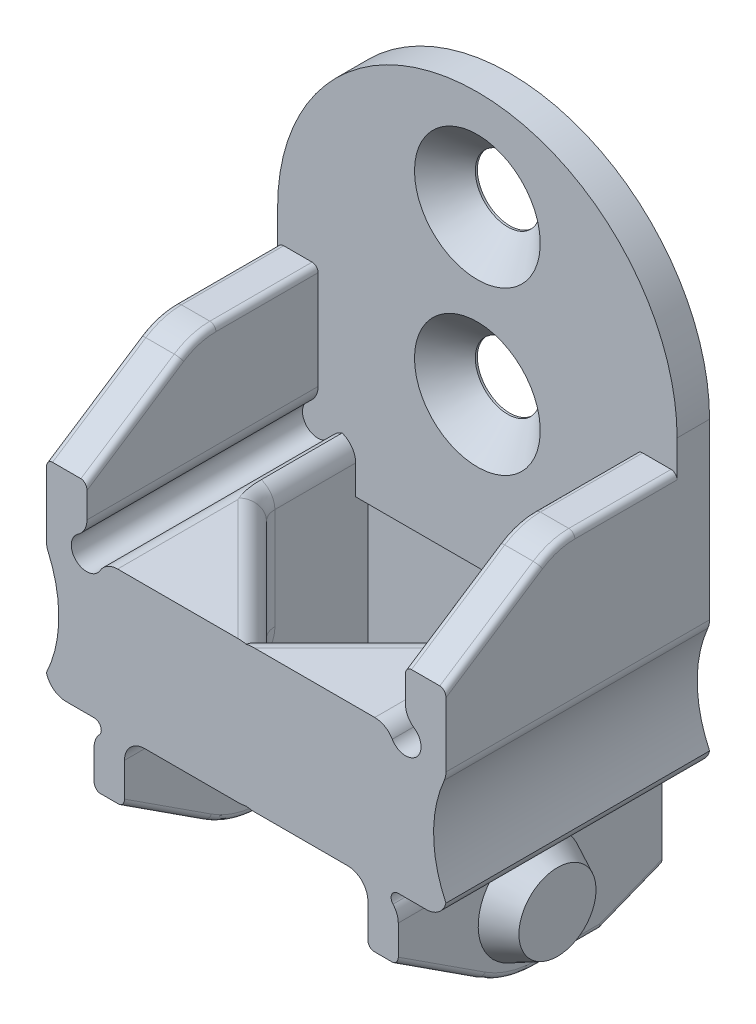
SolidWorks part; units mm, degrees
material "PS HI"
ref_plane "Спереди" through (0, 0, 0) normal (0, 0, 1) x (1, 0, 0)
ref_plane "Сверху" through (0, 0, 0) normal (0, 1, 0) x (1, 0, 0)
ref_plane "Справа" through (0, 0, 0) normal (1, 0, 0) x (0, 0, -1)
sketch "Эскиз1" plane through (0, 0, 0) normal (0, 0, 1) x (1, 0, 0)
  line L0 (0, 5.8222) -> (0, -7.793) construction
  line L1 (-6, -3.5) -> (0, -3.5)
  line L3 (-7.1103, 3.5) -> (0, 3.5)
  line L7 (-7.85, -3.4318) -> (-9.85, -3.4318)
  line L8 (-7.85, 4.1458) -> (-7.85, 10)
  line L9 (-7.85, 10) -> (-9.85, 10)
  line L10 (-9.85, -3.4318) -> (-9.85, 10)
  line L11 (-7.85, -3.4318) -> (-7.5, -3.4318)
  line L14 (-7.5, -4.1389) -> (-7.5, -10)
  line L17 (-7.5, -4.1389) -> (-7.5, -10)
  line L18 (-7.5, -10) -> (-6, -10)
  line L19 (-6, -3.5) -> (-6, -10)
  arc A0 (-7.5, -3.4318) -> (-7.5, -4.1389) centre (-7.5, -3.7853) cw
  arc A1 (-7.85, 4.1458) -> (-7.1103, 3.5) centre (-7.8627, 3.3848) ccw
  point P0 (0, 0)
  dimension "D1" = 2
  dimension "D2" = 7
  dimension "D3" = 0.35
  dimension "D4" = 6.5
  dimension "D5" = 6.5
  dimension "D6" = 1.5
  dimension "D7" = 6
  dimension "D8" = 3.5
  dimension "D9" = 9.85
extrude "Бобышка-Вытянуть1" add sketch "Эскиз1" along normal blind 13
chamfer "Фаска1" distance 5.4 angle 33.3 1 edges at (-8.85, 10, 13)
sketch "Эскиз2" plane through (0, 3.5, 0) normal (0, 1, 0) x (1, 0, 0)
  line L0 (0, -13) -> (0, 0) construction
  line L1 (0, -1) -> (-6, -1)
  line L2 (0, -1) -> (0, -12)
  line L3 (0, -12) -> (-6, -12)
  line L4 (-6, -1) -> (-6, -12)
  line L5 (-7.1103, 0) -> (0, 0) construction
  line L6 (-7.1103, -13) -> (0, -13) construction
  line L7 (-6, -13) -> (-6, 0) construction
  dimension "D1" = 1
  dimension "D2" = 1
extrude "Вырез-Вытянуть1" cut sketch "Эскиз2" against normal through all
ref_plane "Плоскость1" through (0, 0, 6.5) normal (0, 0, -1) x (-1, 0, 0)
fillet "Скругление3" radius 3.2 1 edges at (-8.85, 10, 7.6)
sketch "Эскиз5" plane through (-7.5, 0, 0) normal (-1, 0, 0) x (0, 0, 1)
  line L0 (0, -10) -> (0, -8.8044)
  line L1 (0, -4.1389) -> (0, -10) construction
  line L3 (0, -8.8044) -> (3.0199, -10)
  line L4 (13, -10) -> (0, -10) construction
  line L5 (3.0199, -10) -> (0, -10)
extrude "Вырез-Вытянуть2" cut sketch "Эскиз5" against normal up to next
sketch "Эскиз7" plane through (0, 0, 13) normal (0, 0, 1) x (1, 0, 0)
  line L0 (-9.85, -3.4318) -> (-9.85, 6.4529) construction
  line L1 (-9.85, 2.7085) -> (-9.85, -2.673)
  line L2 (-9.85, -3.4318) -> (-9.85, 6.4529) construction
  arc A0 (-9.85, -2.673) -> (-9.85, 2.7085) centre (-15.4901, 0.0178) ccw
extrude "Вырез-Вытянуть4" cut sketch "Эскиз7" against normal up to next
sketch "Эскиз10" plane through (0, 0, 6.5) normal (0, 0, -1) x (-1, 0, 0)
  line L0 (9.6131, -6.8) -> (2.6205, -6.8) construction
  line L1 (6, -3.5) -> (0, -3.5) construction
  line L2 (13.5674, 6.8) -> (4.1326, 6.8) construction
  line L3 (7.1103, 3.5) -> (0, 3.5) construction
  line L4 (7.85, 6.8) -> (8.85, 6.8)
  line L5 (8.85, 6.8) -> (8.85, 8.8)
  line L6 (8.85, 8.8) -> (7.85, 9.2877)
  line L8 (7.85, 9.2877) -> (7.85, 6.8)
  line L10 (7.5, -6.8) -> (7.5, -4.2416)
  line L11 (7.5, -4.1389) -> (7.5, -10) construction
  line L12 (7.5, -4.2416) -> (8.85, -4.9)
  line L13 (8.85, -4.9) -> (8.85, -6.8)
  line L14 (8.85, -6.8) -> (7.5, -6.8)
  line L17 (7.85, 9.4746) -> (7.85, 6.4529) construction
  dimension "D1" = 3.3
  dimension "D2" = 3.3
  dimension "D3" = 2
  dimension "D4" = 1
  dimension "D5" = 64
  dimension "D6" = 64
  dimension "D7" = 1.9
revolve "Повернуть2" add sketch "Эскиз10" angle 360 about L0
sketch "Эскиз11" plane through (-6, 0, 0) normal (1, 0, 0) x (0, 0, -1)
  line L0 (-7.6293, -10) -> (-13, -6.5141)
  line L1 (-13, -10) -> (-3.0199, -10) construction
  line L2 (-13, -3.5) -> (-13, -10) construction
  line L4 (-13, -6.5141) -> (-13, -10)
  line L5 (-13, -10) -> (-7.6293, -10)
extrude "Вырез-Вытянуть7" cut sketch "Эскиз11" against normal blind 10
fillet "Скругление7" radius 5 1 edges at (-6.75, -10, 7.6293)
chamfer "Фаска2" distance 6 angle 45 1 edges at (-6, 0, 12)
sketch "Эскиз12" plane through (0, 0, 1) normal (0, 0, 1) x (1, 0, 0)
  line L0 (-6, -3.5) -> (-6, -8.8044)
  line L1 (-6, -8.8044) -> (0, -8.8044)
  line L2 (0, -8.8044) -> (0, -3.5)
  line L4 (0, -3.5) -> (-6, -3.5)
extrude "Бобышка-Вытянуть2" add sketch "Эскиз12" against normal up to surface (1 mm away) up to face at (-6.9022, -0.3887, 0)
fillet "Скругление11" radius 1 5 edges at (-6, 3.5, 3.5) (-3, 3.5, 9) (-3, -3.5, 9) (-6, 0, 6) (-6, -3.5, 9.5)
fillet "Скругление13" radius 1 2 edges at (-9.85, 2.7085, 6.5) (-9.85, -3.4318, 6.5)
fillet "Скругление12" radius 1 3 edges at (-7.5, -4.1389, 6.5) (-7.1103, 3.5, 6.5) (-7.85, 4.1458, 6.5)
fillet "Скругление14" radius 0.3 14 edges at (-7.5, -10, 4.5844) (-7.5, -7.8541, 10.9355) (-6, -7.8541, 10.9355) (-6, -9.7943, 7.5683) (-9.85, 7.9637, 10.6999) (-9.85, 9.8658, 7.5599) (-7.85, 7.9637, 10.6999) (-7.85, 9.8658, 7.5599) (-7.5, -9.7943, 7.5683) (-7.5, -9.4022, 1.51) (-6, -9.4022, 1.51) (-6, -10, 4.5844) (-9.85, 10, 3.3215) (-7.85, 10, 3.3215)
sketch "Эскиз13" plane through (0, 0, 0) normal (0, 0, -1) x (-1, 0, 0)
  line L0 (7.85, 4.8432) -> (7.85, 9.7) construction
  line L1 (9.85, 2.9261) -> (9.85, 9.7) construction
  line L2 (7.85, 7.4921) -> (9.85, 7.4921)
  arc A0 (7.85, 7.4921) -> (9.85, 7.4921) centre (8.85, 9.9699) cw
extrude "Бобышка-Вытянуть3" [suppressed] add sketch "Эскиз13" against normal blind 0.2
sketch "Эскиз15" plane through (0, 0, 0) normal (0, 0, -1) x (-1, 0, 0)
  line L3 (0, 3.5) -> (0, -8.8044) construction
  line L4 (0, 1.9519) -> (9.0645, 1.9519)
  line L5 (9.85, 2.9261) -> (9.85, 11.4926)
  line L6 (0, 21.3426) -> (0, 18.0257)
  line L7 (9.0645, 1.9519) -> (9.85, 2.9261)
  line L8 (0, 14.8257) -> (0, 10.0257)
  line L9 (0, 6.8257) -> (0, 1.9519)
  arc A1 (9.85, 11.4926) -> (0, 21.3426) centre (0, 11.4926) ccw
  arc A2 (0, 14.8257) -> (0, 18.0257) centre (0, 16.4257) ccw
  arc A3 (0, 6.8257) -> (0, 10.0257) centre (0, 8.4257) ccw
  dimension "D1" = 3.2
  dimension "D2" = 8
extrude "Бобышка-Вытянуть4" add sketch "Эскиз15" against normal blind 1.6
chamfer "Фаска3" distance 1.5 angle 45 3 edges at (-3, 1.9519, 1) (-1.6, 8.4257, 1.6) (-1.6, 16.4257, 1.6)
mirror "Зеркальное отражение1" about plane through (0, 0, 13) normal (1, 0, 0) of bodies 119 115
